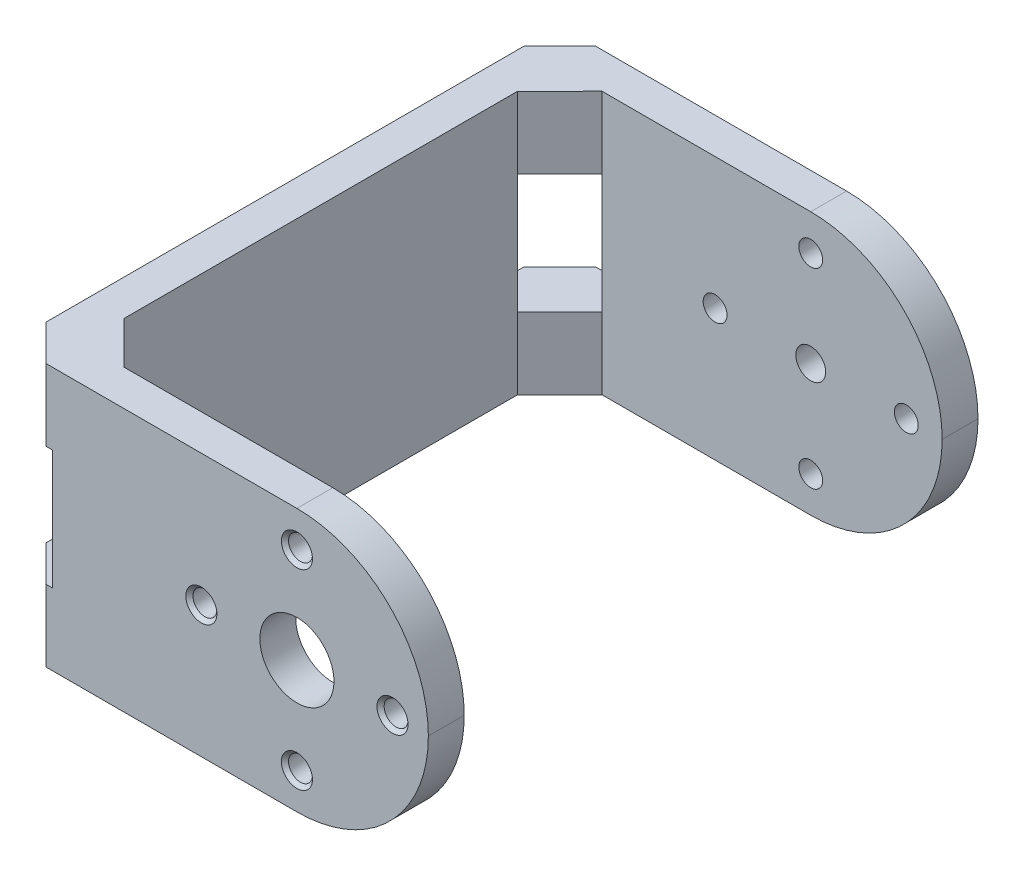
SolidWorks part; units mm, degrees
material "ABS"
ref_plane "Ön Düzlem" through (0, 0, 0) normal (0, 0, 1) x (1, 0, 0)
ref_plane "Üst Düzlem" through (0, 0, 0) normal (0, 1, 0) x (1, 0, 0)
ref_plane "Sağ Düzlem" through (0, 0, 0) normal (1, 0, 0) x (0, 0, -1)
sketch "Çizim1" plane through (0, 0, 0) normal (1, 0, 0) x (0, 0, -1)
  line L1 (-23, 11) -> (23, 11)
  line L2 (-23, 11) -> (-23, -11)
  line L3 (-23, -11) -> (23, -11)
  line L4 (23, 11) -> (23, -11)
  line L5 (-23, 11) -> (23, -11) construction
  line L6 (-23, -11) -> (23, 11) construction
  point P0 (0, 0)
  dimension "D1" = 22
  dimension "D2" = 46
extrude "Yükseklik-Ekstrüzyon1" add sketch "Çizim1" along normal blind 35
sketch "Çizim2" plane through (35, 0, 0) normal (1, 0, 0) x (0, 0, -1)
  line L0 (-23, -11) -> (23, -11) construction
  line L1 (-20, 11) -> (20, 11)
  line L2 (-20, 11) -> (-20, -11)
  line L3 (-20, -11) -> (20, -11)
  line L4 (20, 11) -> (20, -11)
  line L5 (-20, 11) -> (20, -11) construction
  line L6 (-20, -11) -> (20, 11) construction
  point P0 (0, 0)
  dimension "D1" = 40
extrude "Kes-Ekstrüzyon1" cut sketch "Çizim2" against normal blind 32
fillet "Radyus1" radius 11 4 edges at (35, -11, 21.5) (35, 11, 21.5) (35, -11, -21.5) (35, 11, -21.5)
chamfer "Pah1" distance 3 angle 45 2 edges at (0, 0, 23) (0, 0, -23)
ref_plane "Kablo Deliği Referansı" through (-10, 0, 10) normal (-0.7071, 0, 0.7071) x (0.7071, 0, 0.7071)
sketch "Çizim3" plane through (-10, 0, 10) normal (-0.7071, 0, 0.7071) x (0.7071, 0, 0.7071)
  line L1 (13.7621, 5) -> (18.7621, 5)
  line L2 (13.7621, 5) -> (13.7621, -5)
  line L3 (13.7621, -5) -> (18.7621, -5)
  line L4 (18.7621, 5) -> (18.7621, -5)
  line L5 (13.7621, 5) -> (18.7621, -5) construction
  line L6 (13.7621, -5) -> (18.7621, 5) construction
  line L7 (14.1421, 11) -> (18.3848, 11) construction
  line L8 (14.1421, -11) -> (14.1421, 11) construction
  point P0 (16.2621, 0)
  dimension "D1" = 5
  dimension "D2" = 10
  dimension "D3" = 11
  dimension "D4" = 2.12
extrude "Kes-Ekstrüzyon2" cut sketch "Çizim3" against normal blind 20
sketch "Vida Deliği Refarans" plane through (0, 0, 23) normal (0, 0, 1) x (1, 0, 0)
  circle A0 centre (24, 0) radius 8
  point P3 (32, 0)
  point P4 (24, 8)
  point P5 (16, 0)
  point P6 (24, -8)
  dimension "D1" = 8
hole_wizard "M2 Düz Başlı Makine Vidası İçin Havşa1" positions "3B Çizim1" profile "Çizim5" countersink size "M2" standard "ANSI Metrik" end condition up to next
sketch3d "3B Çizim1"
  point P0 (16, 0, 23)
  point P3 (24, 8, 23)
  point P6 (32, 0, 23)
  point P9 (24, -8, 23)
sketch "Çizim5" plane through (16, 0, 23) normal (1, 0, 0) x (0, -1, 0)
  line L0 (0, 0) -> (0, 46)
  line L1 (0, 46) -> (1, 46)
  line L2 (1, 46) -> (1, 0.3)
  line L3 (1, 0.3) -> (1.3, 0)
  line L5 (1.3, 0) -> (0, 0)
  line L6 (-1, 0.3) -> (-1.3, 0) construction
  line L11 (0, -6.35) -> (0, 107.95) construction
  dimension "Thru Hole Dia." = 2
  dimension "Thru Hole Depth" = 46
  dimension "Near C'Sink Dia." = 2.6
  dimension "Near C'Sink Angle" = 90
mirror "Aynalama2" about plane through (0, 0, 0) normal (0, 0, 1) of "M2 Düz Başlı Makine Vidası İçin Havşa1", "Kes-Ekstrüzyon2"
sketch "Çizim8" plane through (0, -5, 0) normal (0, 1, 0) x (1, 0, 0)
  line L0 (6.5337, 20) -> (3, 16.4626)
rib "Feder5" sketch "Çizim8" sketch "Çizim8" thickness 6 extrusion direction parallel to sketch draft on no parameters "D1"=6
mirror "Aynalama3" about plane through (0, 0, 0) normal (0, 1, 0) of "Feder5"
mirror "Aynalama4" about plane through (0, 0, 0) normal (0, 0, 1) of "Aynalama3", "Feder5"
sketch "Çizim10" plane through (0, 0, -23) normal (0, 0, -1) x (-1, 0, 0)
  circle A0 centre (-24, 0) radius 3.1
  dimension "D1" = 6.2
extrude "Kes-Ekstrüzyon4" cut sketch "Çizim10" against normal through all
sketch "Çizim12" plane through (0, 0, -23) normal (0, 0, -1) x (-1, 0, 0)
  circle A1 centre (-24, 0) radius 3.1
  point P4 (-24, 0)
  dimension "D1" = 6.2
extrude "Yükseklik-Ekstrüzyon3" add sketch "Çizim12" against normal blind 3
hole_wizard "M3 Düz Başlı Makine Vidası İçin Havşa1" positions "3B Çizim4" profile "Çizim17" countersink size "M3" standard "ANSI Metrik"
sketch3d "3B Çizim4"
  point P0 (24, 0, -23)
sketch "Çizim17" plane through (24, 0, -23) normal (1, 0, 0) x (0, 1, 0)
  line L0 (0, 0) -> (0, 3)
  line L1 (0, 3) -> (1.25, 3)
  line L2 (1.25, 3) -> (1.25, 0.3)
  line L3 (1.25, 0.3) -> (1.55, 0)
  line L5 (1.55, 0) -> (0, 0)
  line L6 (-1.25, 0.3) -> (-1.55, 0) construction
  line L10 (0, 3) -> (-1.25, 3) construction
  line L11 (0, -6.35) -> (0, 107.95) construction
  dimension "Hole Dia." = 2.5
  dimension "Hole Depth" = 3
  dimension "Near C'Sink Dia." = 3.1
  dimension "Near C'Sink Angle" = 90
  dimension "Drill Angle" = 180
